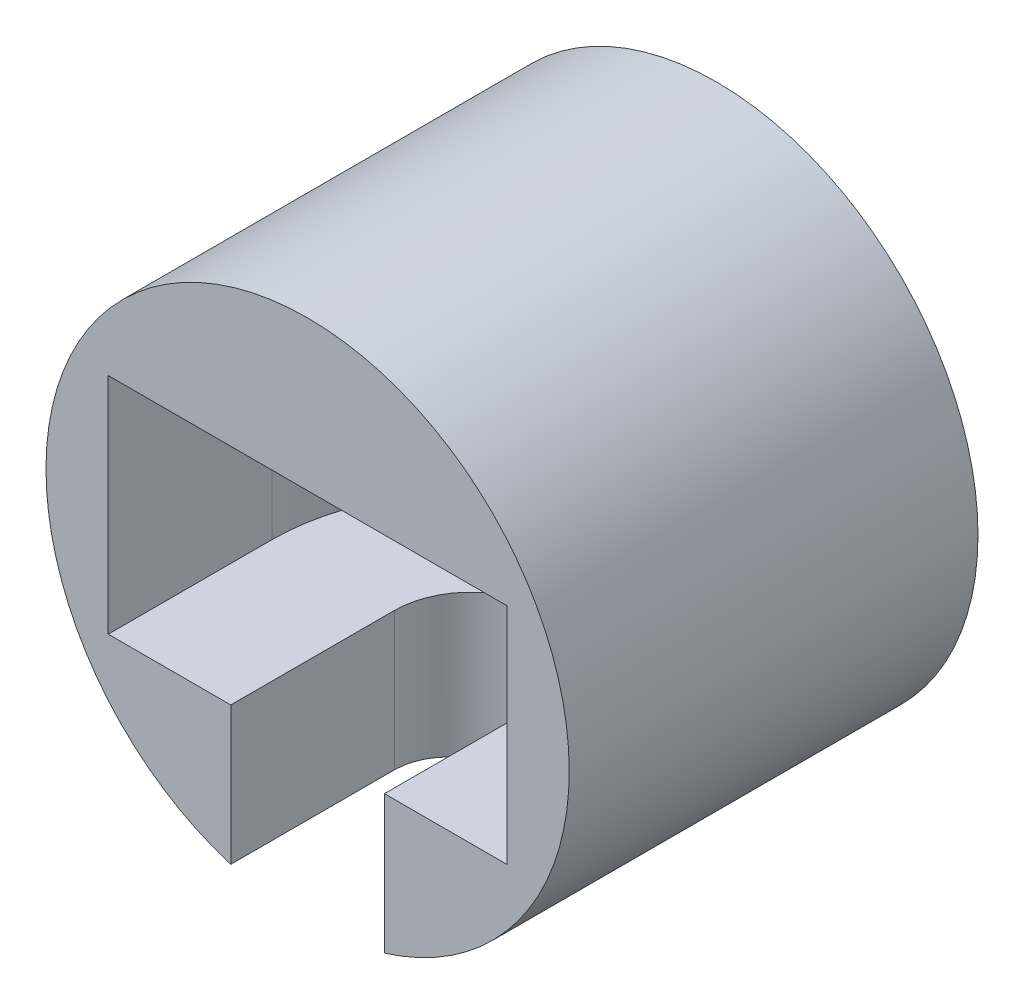
SolidWorks part; units mm, degrees
ref_plane "Front Plane" through (0, 0, 0) normal (0, 0, 1) x (1, 0, 0)
ref_plane "Top Plane" through (0, 0, 0) normal (0, 1, 0) x (1, 0, 0)
ref_plane "Right Plane" through (0, 0, 0) normal (1, 0, 0) x (0, 0, -1)
sketch "Sketch1" plane through (0, 0, 0) normal (0, 0, 1) x (1, 0, 0)
  circle A0 centre (0, 0) radius 16
  circle A1 centre (0, 0) radius 3
extrude "Boss-Extrude1" add sketch "Sketch1" along normal blind 25
sketch "Sketch2" plane through (0, 0, 0) normal (0, 1, 0) x (1, 0, 0)
  line L5 (-12.193, -25) -> (12.193, -25)
  line L17 (-12.193, -15) -> (-12.193, -25)
  line L18 (12.193, -15) -> (12.193, -25)
  arc A5 (-12.193, -15) -> (12.193, -15) centre (0, -15) cw
extrude "Cut-Extrude1" cut sketch "Sketch2" against normal mid plane 13.7
sketch "Sketch3" plane through (0, 0, 0) normal (0, 1, 0) x (1, 0, 0)
  line L5 (-4.7, -15) -> (-4.7, -25)
  line L6 (-4.7, -25) -> (4.7, -25)
  line L7 (4.7, -15) -> (4.7, -25)
  arc A1 (4.7, -15) -> (-4.7, -15) centre (0, -15) ccw
extrude "Cut-Extrude2" cut sketch "Sketch3" against normal up to surface (15.2941 mm away) up to face at (16, 0, 25)
